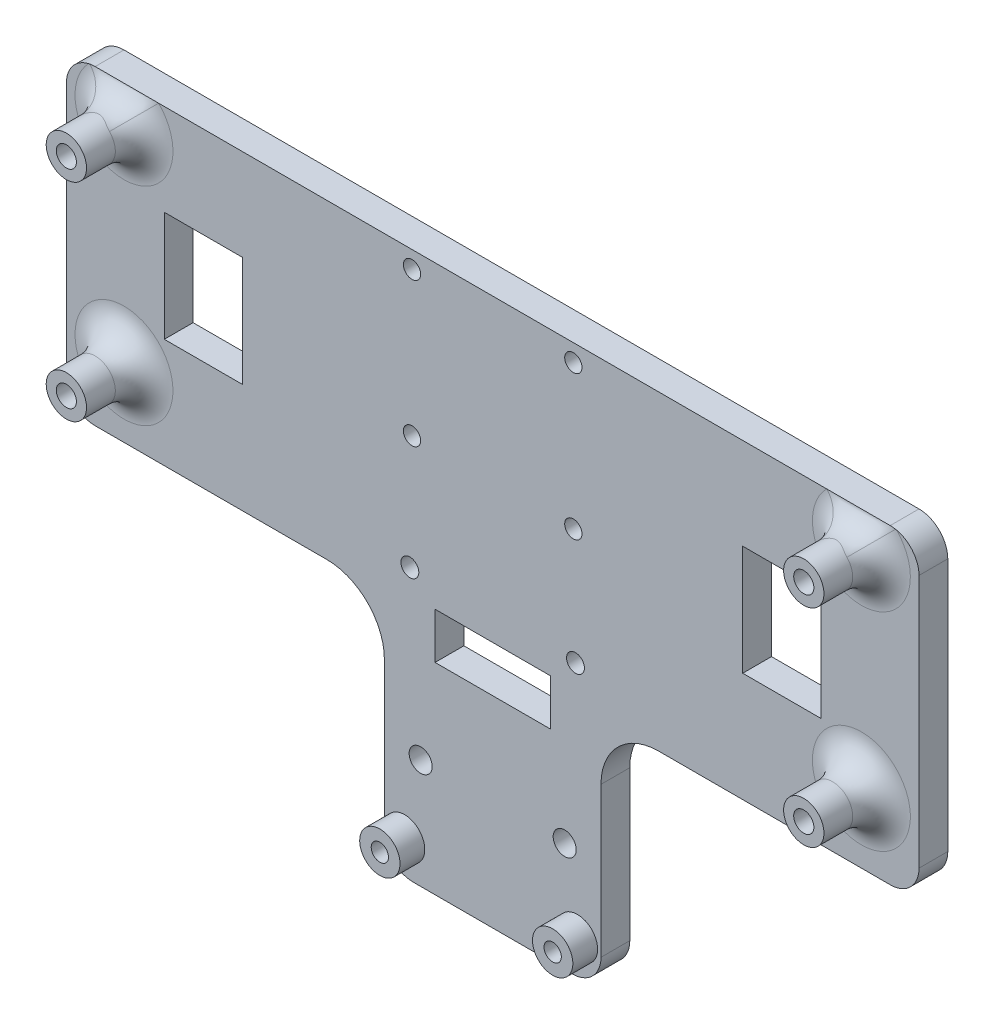
SolidWorks part; units mm, degrees
ref_plane "Front Plane" through (0, 0, 0) normal (0, 0, 1) x (1, 0, 0)
ref_plane "Top Plane" through (0, 0, 0) normal (0, 1, 0) x (1, 0, 0)
ref_plane "Right Plane" through (0, 0, 0) normal (1, 0, 0) x (0, 0, -1)
sketch "Sketch1" plane through (0, 0, 0) normal (0, 1, 0) x (1, 0, 0)
  line L0 (0, 0) -> (0, 178.218) construction
  line L1 (61, 138.218) -> (74, 138.218)
  line L2 (74, 138.218) -> (74, 181.218)
  line L3 (74, 181.218) -> (-74, 181.218)
  line L4 (0, 181.218) -> (0, 178.218)
  line L5 (-71, 178.218) -> (71, 178.218)
  line L6 (71, 178.218) -> (71, 143.218)
  line L7 (71, 143.218) -> (61, 143.218)
  line L8 (61, 143.218) -> (61, 138.218)
  line L9 (-61, 143.218) -> (-61, 138.218)
  line L10 (-71, 143.218) -> (-61, 143.218)
  line L11 (-71, 178.218) -> (-71, 143.218)
  line L12 (-74, 138.218) -> (-74, 181.218)
  line L13 (-61, 138.218) -> (-74, 138.218)
  dimension "D1" = 10
  dimension "D2" = 5
  dimension "D3" = 74
  dimension "D4" = 3
  dimension "D5" = 3
  dimension "D6" = 35
extrude "Boss-Extrude1" add sketch "Sketch1" along normal blind 110 contours L13 L9 L10 L11 L5 L4 L3 L12 | L7 L8 L1 L2 L3 L4 L5 L6 region at (61.8559, 0, -140.718) region at (-0.8559, 0, -179.718)
sketch "Sketch2" plane through (74, 0, 0) normal (1, 0, 0) x (0, 0, -1)
  line L0 (138.218, 66.5) -> (165.218, 66.5)
  line L1 (138.218, 110) -> (138.218, 0) construction
  line L2 (165.218, 66.5) -> (165.218, 100.5)
  line L3 (165.218, 100.5) -> (138.218, 100.5)
  line L4 (138.218, 100.5) -> (138.218, 66.5)
  line L5 (138.218, 110) -> (181.218, 110) construction
  dimension "D1" = 34
  dimension "D2" = 9.5
  dimension "D3" = 27
extrude "Cut-Extrude1" cut sketch "Sketch2" against normal blind 171
sketch "Sketch5" plane through (0, 0, -138.218) normal (0, 0, 1) x (1, 0, 0)
  line L0 (-61, 66.5) -> (-71, 66.5)
  line L1 (-74, 66.5) -> (-61, 66.5) construction
  line L2 (-71, 66.5) -> (-71, 54)
  line L3 (-71, 54) -> (-61, 54)
  line L4 (-61, 66.5) -> (-61, 0) construction
  line L5 (-61, 54) -> (-61, 66.5)
  line L6 (0, 0) -> (0, 110) construction
  line L7 (-71, 0) -> (71, 0) construction
  line L8 (-71, 110) -> (71, 110) construction
  line L9 (61, 54) -> (61, 66.5)
  line L10 (71, 54) -> (61, 54)
  line L11 (71, 66.5) -> (71, 54)
  line L12 (61, 66.5) -> (71, 66.5)
  dimension "D1" = 12.5
extrude "Cut-Extrude4" cut sketch "Sketch5" against normal blind 10 contours L5 L0 L2 L3 | L9 L12 L11 L10
sketch "Sketch7" plane through (74, 0, 0) normal (1, 0, 0) x (0, 0, -1)
  line L0 (181.218, 110) -> (138.218, 110)
  line L1 (138.218, 110) -> (138.218, 54)
  line L2 (138.218, 66.5) -> (138.218, 0) construction
  line L3 (138.218, 54) -> (181.218, 54)
  line L4 (181.218, 110) -> (181.218, 0) construction
  line L5 (181.218, 54) -> (181.218, 110)
  dimension "D1" = 56
extrude "Cut-Extrude5" cut sketch "Sketch7" against normal blind 280
sketch "Sketch9" plane through (0, 0, -181.218) normal (0, 0, -1) x (-1, 0, 0)
  line L0 (0, 0) -> (0, -92.5) construction
  line L1 (-75, -92.5) -> (75, -92.5) construction
  line L2 (18.8, 0) -> (18.8, -41)
  line L3 (-74, 0) -> (74, 0) construction
  line L4 (18.8, -41) -> (-18.8, -41)
  line L5 (0, -41) -> (0, 0)
  line L6 (-18.8, 0) -> (18.8, 0)
  line L7 (-18.8, 0) -> (-18.8, -41)
  circle A0 centre (15.285, -35.0992) radius 1.5
  circle A1 centre (-14.715, -35.0992) radius 1.5
  line M9 (-74, 0) -> (74, 0)
  dimension "D1" = 18.8
  dimension "D2" = 41
extrude "Boss-Extrude3" add sketch "Sketch9" against normal blind 3 contours L5 L4 L2 A0 M9 | L7 L4 L5 A1 M9 region at (-9.3455, -20.3649, -181.218) region at (9.3508, -20.3649, -181.218)
fillet "Fillet2" radius 10 4 edges at (-71, 27, -178.218) (71, 27, -178.218) (-18.8, 0, -179.718) (18.8, 0, -179.718)
sketch "Sketch11" plane through (0, 0, -181.218) normal (0, 0, -1) x (-1, 0, 0)
  line L0 (43.7, 19.3) -> (43.7, 37.8)
  line L1 (43.7, 37.8) -> (56.7, 37.8)
  line L2 (56.7, 37.8) -> (56.7, 19.3)
  line L3 (56.7, 19.3) -> (43.7, 19.3)
  circle A0 centre (-14, 51) radius 1.5
  circle A1 centre (-14, 26) radius 1.5
  circle A2 centre (14, 26) radius 1.5
  circle A3 centre (14, 51) radius 1.5
extrude "Cut-Extrude6" cut sketch "Sketch11" against normal blind 4.3
sketch "Sketch12" plane through (0, 0, -181.218) normal (0, 0, -1) x (-1, 0, 0)
  line L0 (18.8, -41) -> (-18.8, -41) construction
  line L26 (-6.8, -11.075) -> (-6.8, -30.175)
  line L27 (6.8, -30.175) -> (6.8, -11.075)
  line L28 (6.8, -11.075) -> (-6.8, -11.075)
  line L29 (-6.8, -30.175) -> (6.8, -30.175)
  dimension "D1" = 10.825
  dimension "D2" = 19.1
extrude "Cut-Extrude7" cut sketch "Sketch12" against normal blind 4.3
sketch "Sketch13" plane through (0, 0, -138.218) normal (0, 0, 1) x (1, 0, 0)
  circle A0 centre (64, 12) radius 2.25
  circle A1 centre (64, 48) radius 2.25
  circle A2 centre (-64, 12) radius 2.25
  circle A3 centre (-64, 48) radius 2.25
extrude "Cut-Extrude8" cut sketch "Sketch13" against normal blind 5
sketch "Sketch15" plane through (74, 0, 0) normal (1, 0, 0) x (0, 0, -1)
  line L0 (138.218, 54) -> (138.218, 45)
  line L1 (138.218, 54) -> (138.218, 0) construction
  line L2 (138.218, 45) -> (153.218, 45)
  line L3 (153.218, 45) -> (153.218, 30)
  line L4 (153.218, 30) -> (138.218, 30)
  line L5 (138.218, 30) -> (138.218, 45)
  line L6 (138.218, 54) -> (181.218, 54) construction
  line M5 (138.218, 54) -> (138.218, 0)
  dimension "D1" = 9
  dimension "D2" = 15
  dimension "D3" = 15
extrude "Cut-Extrude10" cut sketch "Sketch15" against normal blind 15.3 contours L4 L3 L2 M5 region at (74, 37.5, -145.718)
sketch "Sketch16" plane through (0, -41, 0) normal (0, -1, 0) x (-1, 0, 0)
  line L1 (-74, 178.218) -> (-74, 138.218)
  line L2 (-74, 138.218) -> (-61, 138.218)
  line L3 (-61, 138.218) -> (-61, 143.218)
  line L4 (-61, 143.218) -> (-71, 143.218)
  line L5 (-71, 143.218) -> (-18.8, 178.218)
  line L6 (0, 181.218) -> (0, 201.6639)
  line L7 (18.8, 181.218) -> (-18.8, 181.218) construction
  line L10 (71, 143.218) -> (18.8, 178.218)
  line L11 (61, 143.218) -> (71, 143.218)
  line L12 (61, 138.218) -> (61, 143.218)
  line L13 (74, 138.218) -> (61, 138.218)
  line L16 (-18.8, 178.218) -> (-74, 178.218)
  line L17 (18.8, 178.218) -> (74, 178.218)
  line L18 (74, 138.218) -> (74, 181.218) construction
  line L19 (74, 178.218) -> (74, 138.218)
extrude "Cut-Extrude11" cut sketch "Sketch16" against normal through all contours L19 L17 L10 L11 L12 L13 | L5 L16 L1 L2 L3 L4 region at (56.2654, -41, -164.4363) region at (-56.2654, -41, -164.4363)
sketch "Sketch17" plane through (0, 0, -178.218) normal (0, 0, 1) x (1, 0, 0)
  circle A0 centre (64, 12) radius 1.75
  circle A1 centre (64, 48) radius 1.75
  circle A2 centre (-64, 48) radius 1.75
  circle A3 centre (-64, 12) radius 1.75
  dimension "D1" = 3.5
  dimension "D2" = 3.5
  dimension "D3" = 3.5
  dimension "D4" = 3.5
extrude "Cut-Extrude12" cut sketch "Sketch17" against normal blind 10
sketch "Sketch18" plane through (0, 0, -178.218) normal (0, 0, 1) x (1, 0, 0)
  circle A0 centre (64, 12) radius 3.5
  circle A1 centre (64, 48) radius 3.5
  circle A2 centre (-64, 48) radius 3.5
  circle A3 centre (-64, 12) radius 3.5
  circle A4 centre (64, 48) radius 1.75
  circle A5 centre (64, 12) radius 1.75
  circle A6 centre (-64, 12) radius 1.75
  circle A7 centre (-64, 48) radius 1.75
  dimension "D1" = 7
  dimension "D2" = 7
  dimension "D3" = 7
  dimension "D4" = 7
extrude "Boss-Extrude5" add sketch "Sketch18" along normal blind 10
sketch "Sketch19" plane through (0, 0, -181.218) normal (0, 0, -1) x (-1, 0, 0)
  line L0 (0, -11.075) -> (0, 54) construction
  line L1 (6.8, -11.075) -> (-6.8, -11.075) construction
  line L2 (74, 54) -> (-74, 54) construction
  line L3 (10, -6.075) -> (-10, -6.075)
  line L4 (-10, -6.075) -> (-10, 1.925)
  line L5 (-10, 1.925) -> (10, 1.925)
  line L6 (10, 1.925) -> (10, -6.075)
  dimension "D1" = 20
  dimension "D2" = 10
  dimension "D3" = 8
  dimension "D4" = 5
extrude "Cut-Extrude13" cut sketch "Sketch19" against normal blind 10
sketch "Sketch20" plane through (0, 0, -181.218) normal (0, 0, -1) x (-1, 0, 0)
  line L5 (-43.4, 19) -> (-57, 19)
  line L6 (-57, 19) -> (-57, 38.1)
  line L7 (-57, 38.1) -> (-43.4, 38.1)
  line L8 (-43.4, 38.1) -> (-43.4, 19)
  line L9 (-74, 54) -> (-74, 0) construction
  line L10 (-74, 0) -> (-28.8, 0) construction
  dimension "D3" = 19.1
  dimension "D4" = 13.6
  dimension "D5" = 17
  dimension "D6" = 19
extrude "Cut-Extrude14" cut sketch "Sketch20" against normal blind 10
sketch "Sketch21" plane through (0, 0, -181.218) normal (0, 0, -1) x (-1, 0, 0)
  line L0 (74, 0) -> (74, 54)
  line L1 (74, 54) -> (-74, 54)
  line L2 (-74, 54) -> (-74, 0)
  line L3 (-74, 0) -> (-28.8, 0)
  line L4 (-18.8, -10) -> (-18.8, -41)
  line L5 (-18.8, -41) -> (18.8, -41)
  line L6 (18.8, -41) -> (18.8, -10)
  line L7 (28.8, 0) -> (74, 0)
  line L8 (6.8, -30.175) -> (6.8, -11.075)
  line L9 (6.8, -11.075) -> (-6.8, -11.075)
  line L10 (-6.8, -11.075) -> (-6.8, -30.175)
  line L11 (-6.8, -30.175) -> (6.8, -30.175)
  line L12 (-10, 1.925) -> (-10, -6.075)
  line L13 (-10, -6.075) -> (10, -6.075)
  line L14 (10, -6.075) -> (10, 1.925)
  line L15 (10, 1.925) -> (-10, 1.925)
  line L16 (-43.4, 19) -> (-43.4, 38.1)
  line L17 (-43.4, 38.1) -> (-57, 38.1)
  line L18 (-57, 38.1) -> (-57, 19)
  line L19 (-57, 19) -> (-43.4, 19)
  arc A0 (-28.8, 0) -> (-18.8, -10) centre (-28.8, -10) cw
  arc A1 (18.8, -10) -> (28.8, 0) centre (28.8, -10) cw
  arc A2 (28.8, 0) -> (18.8, -10) centre (28.8, -10) ccw construction
  circle A3 centre (15.285, -35.0992) radius 1.5
  circle A4 centre (-14.715, -35.0992) radius 1.5
  circle A5 centre (-14, 26) radius 1.5
  circle A6 centre (-14, 51) radius 1.5
  circle A7 centre (-64, 12) radius 1.75
  circle A8 centre (-64, 48) radius 1.75
  circle A9 centre (14, 51) radius 1.5
  circle A10 centre (14, 26) radius 1.5
  circle A11 centre (64, 12) radius 1.75
  circle A12 centre (64, 48) radius 1.75
  circle A13 centre (12.5, -22) radius 2
  circle A14 centre (-12.5, -22) radius 2
extrude "Boss-Extrude6" add sketch "Sketch21" along normal blind 2
fillet "Fillet3" radius 5 4 edges at (-67.5, 12, -178.218) (-67.5, 48, -178.218) (60.5, 48, -178.218) (60.5, 12, -178.218)
fillet "Fillet4" radius 5 6 edges at (-18.8, -41, -180.718) (18.8, -41, -180.718) (-74, 0, -180.718) (-74, 54, -180.718) (74, 54, -180.718) (74, 0, -180.718)
sketch "Sketch10" plane through (0, 0, -178.218) normal (0, 0, 1) x (1, 0, 0)
  circle A0 centre (14.715, -35.0992) radius 3.5
  circle A1 centre (-15.285, -35.0992) radius 3.5
  circle A2 centre (14.715, -35.0992) radius 1.5
  circle A3 centre (-15.285, -35.0992) radius 1.5
  dimension "D1" = 7
  dimension "D2" = 7
extrude "Boss-Extrude4" add sketch "Sketch10" along normal blind 4.3
sketch "Sketch22" plane through (0, 0, -183.218) normal (0, 0, -1) x (-1, 0, 0)
  line L0 (6.8, -30.175) -> (6.8, -11.075)
  line L1 (6.8, -11.075) -> (-6.8, -11.075)
  line L2 (-6.8, -11.075) -> (-6.8, -30.175)
  line L3 (-6.8, -30.175) -> (6.8, -30.175)
extrude "Boss-Extrude7" add sketch "Sketch22" against normal blind 5
sketch "Sketch23" plane through (0, 0, -183.218) normal (0, 0, -1) x (-1, 0, 0)
  line L0 (0, -41) -> (0, 54) construction
  line L1 (-13.8, -41) -> (13.8, -41) construction
  line L2 (69, 54) -> (-69, 54) construction
  line L3 (-43.4, 19) -> (-57, 19)
  line L4 (-57, 19) -> (-57, 38.1)
  line L5 (-57, 38.1) -> (-43.4, 38.1)
  line L6 (-43.4, 38.1) -> (-43.4, 19)
  line L7 (43.4, 38.1) -> (43.4, 19)
  line L8 (57, 38.1) -> (43.4, 38.1)
  line L9 (57, 19) -> (57, 38.1)
  line L10 (43.4, 19) -> (57, 19)
extrude "Cut-Extrude15" cut sketch "Sketch23" against normal blind 5
sketch "Sketch25" plane through (0, 0, -183.218) normal (0, 0, -1) x (-1, 0, 0)
  circle A0 centre (12.5, -22) radius 2
  circle A1 centre (-12.5, -22) radius 2
extrude "Cut-Extrude16" cut sketch "Sketch25" against normal blind 7
sketch "Sketch26" plane through (0, 0, -183.218) normal (0, 0, -1) x (-1, 0, 0)
  circle A0 centre (14.3745, 6.033) radius 1.554
  circle A1 centre (-14.3745, 6.033) radius 1.554
extrude "Cut-Extrude17" cut sketch "Sketch26" against normal blind 10
sketch "Sketch27" plane through (0, 0, -178.218) normal (0, 0, 1) x (1, 0, 0)
  line L0 (-33.7, 19.3) -> (-33.7, 37.8)
  line L1 (-33.7, 37.8) -> (-43.4, 37.8)
  line L2 (-43.4, 37.8) -> (-43.4, 19.3)
  line L3 (-43.4, 19.3) -> (-33.7, 19.3)
extrude "Boss-Extrude8" add sketch "Sketch27" against normal blind 5
